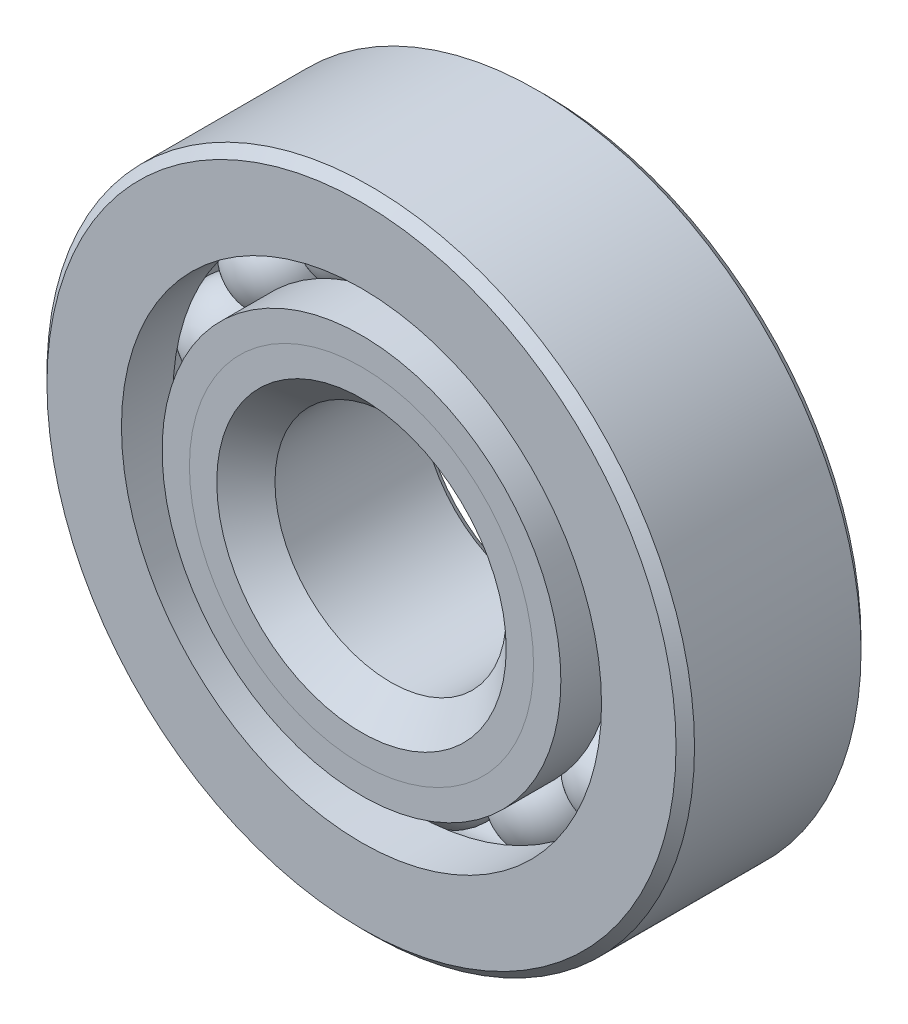
SolidWorks part; units mm, degrees
ref_plane "Front Plane" through (0, 0, 0) normal (0, 0, 1) x (1, 0, 0)
ref_plane "Top Plane" through (0, 0, 0) normal (0, 1, 0) x (1, 0, 0)
ref_plane "Right Plane" through (0, 0, 0) normal (1, 0, 0) x (0, 0, -1)
sketch "Sketch1" plane through (0, 0, 0) normal (1, 0, 0) x (0, 0, -1)
  line L0 (-3.175, 0) -> (3.175, 0) construction
  line L1 (0, 11.1125) -> (0, -11.1125) construction
  line L2 (2.8575, 11.1125) -> (-2.8575, 11.1125)
  line L3 (-2.8575, 11.1125) -> (-3.175, 10.795)
  line L4 (-3.175, 10.795) -> (-3.175, 8.2384)
  line L5 (-3.175, 8.2384) -> (-1.4111, 8.2384)
  line L6 (3.175, 8.2384) -> (1.4111, 8.2384)
  line L7 (3.175, 10.795) -> (3.175, 8.2384)
  line L8 (2.8575, 11.1125) -> (3.175, 10.795)
  line L9 (0, 11.1125) -> (0, 7.5406) construction
  line L10 (0, 7.5406) -> (0, 3.9688) construction
  arc A0 (-1.4111, 8.2384) -> (1.4111, 8.2384) centre (0, 7.5406) cw
  point P14 (0, 3.9688)
  dimension "D3" = 2.8222
  dimension "D1" = 45
  dimension "Width" = 6.35
  dimension "OD" = 22.225
  dimension "D2" = 0.3175
  dimension "Shaft Dia" = 7.9375
  dimension "D4" = 0.6978
revolve "Revolve1" add sketch "Sketch1" angle 360 about L0
sketch "Sketch2" plane through (0, 0, 0) normal (1, 0, 0) x (0, 0, -1)
  line L0 (-3.175, 6.8428) -> (-1.4111, 6.8428)
  line L1 (-3.175, 10.795) -> (-3.175, -10.795) construction
  line L2 (-3.175, 6.8428) -> (-3.175, 5.9052)
  line L3 (-3.175, 5.9052) -> (-2.2374, 4.9676)
  line L4 (-2.2374, 4.9676) -> (0, 4.9676)
  line L5 (0, 11.1125) -> (0, -11.1125) construction
  line L6 (0, 4.9676) -> (0, 5.9664)
  line L7 (0, 5.9664) -> (0, 3.9688) construction
  line L8 (-3.175, 6.8428) -> (-3.175, 4.9676) construction
  line L9 (-3.175, 4.9676) -> (-2.2374, 4.9676) construction
  arc A0 (-1.4111, 6.8428) -> (0, 5.9664) centre (0, 7.5406) ccw
  arc A1 (1.4111, 8.2384) -> (-1.4111, 8.2384) centre (0, 7.5406) ccw construction
  circle A2 centre (0, 7.5406) radius 1.5742 construction
  dimension "D1" = 45
revolve "Revolve2" add sketch "Sketch2" angle 360 about L0
sketch "Sketch3" plane through (0, 0, 0) normal (1, 0, 0) x (0, 0, -1)
  line L0 (-3.175, 5.9052) -> (-2.2374, 4.9676)
  line L1 (-2.2374, 4.9676) -> (0, 4.9676)
  line L2 (0, 4.9676) -> (0, 5.9664)
  line L3 (-3.175, 5.9052) -> (-3.175, 4.9676)
  line L4 (-3.175, 6.8428) -> (-3.175, 4.9676) construction
  line L5 (-3.175, 4.9676) -> (-2.1762, 3.9688)
  line L6 (-2.1762, 3.9688) -> (2.8575, 3.9688)
  line L7 (2.8575, 11.1125) -> (2.8575, -11.1125) construction
  line L8 (2.8575, 3.9688) -> (3.175, 4.2862)
  line L9 (3.175, -10.795) -> (3.175, 10.795) construction
  line L10 (3.175, 4.2862) -> (3.175, 6.8428)
  line L11 (3.175, 6.8428) -> (1.4111, 6.8428)
  line L13 (2.8575, 11.1125) -> (3.175, 10.795) construction
  circle A0 centre (0, 7.5406) radius 1.5742 construction
  arc A1 (1.4111, 6.8428) -> (0, 5.9664) centre (0, 7.5406) cw
revolve "Revolve3" add sketch "Sketch3" angle 360 about L0
sketch "Sketch4" plane through (0, 0, 0) normal (1, 0, 0) x (0, 0, -1)
  line L0 (-1.5742, 7.5406) -> (1.5742, 7.5406)
  circle A1 centre (0, 7.5406) radius 1.5742 construction
  arc A2 (-1.5742, 7.5406) -> (1.5742, 7.5406) centre (0, 7.5406) cw
  arc A3 (1.4111, 8.2384) -> (-1.4111, 8.2384) centre (0, 7.5406) ccw construction
revolve "Revolve4" add sketch "Sketch4" angle 360 about L0
ref_axis "Axis1" through (0, 0, -3.175) along (0, 0, 1)
pattern_circular "CirPattern1" count 14 every 25.714 about axis through (0, 0, -3.175) along (0, 0, 1) of bodies 104
equation "\"D2@Sketch1\" = \"Width@Sketch1\"*.05"
equation "\"D3@Sketch1\" = \"Width@Sketch1\"/2.25"
equation "\"D4@Sketch1\" = (((\"OD@Sketch1\"-\"Width@Sketch1\")/2)/3.25)/3.5"
equation "\"D2@CirPattern1\" = 360/\"Balls@CirPattern1\""
